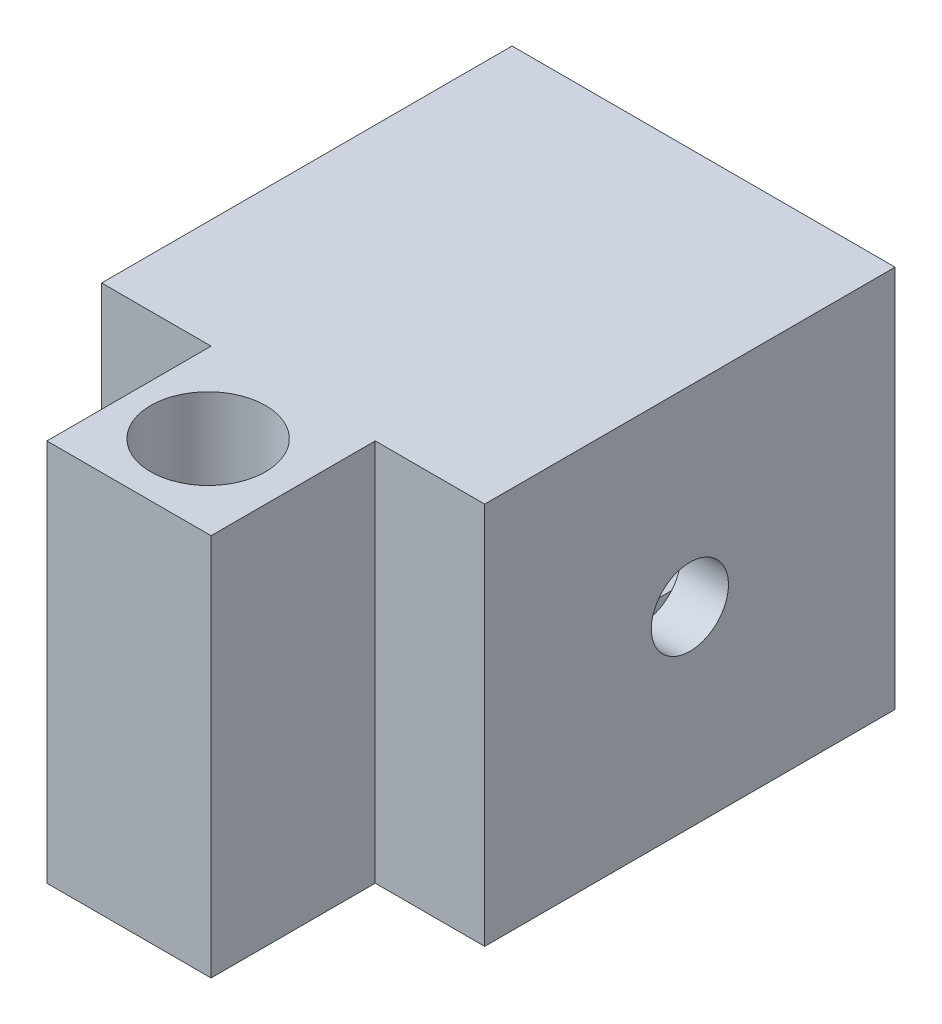
SolidWorks part; units mm, degrees
ref_plane "Спереди" through (0, 0, 0) normal (0, 0, 1) x (1, 0, 0)
ref_plane "Сверху" through (0, 0, 0) normal (0, 1, 0) x (1, 0, 0)
ref_plane "Справа" through (0, 0, 0) normal (1, 0, 0) x (0, 0, -1)
sketch "Эскиз2" plane through (0, 0, 0) normal (0, 0, 1) x (1, 0, 0)
  line L0 (10.5, 0) -> (-10.5, 0)
  line L1 (10.5, 10.5) -> (-10.5, 10.5)
  line L2 (10.5, 10.5) -> (10.5, -10.5)
  line L3 (10.5, -10.5) -> (-10.5, -10.5)
  line L4 (-10.5, 10.5) -> (-10.5, -10.5)
  line L5 (10.5, 10.5) -> (-10.5, -10.5) construction
  line L6 (10.5, -10.5) -> (-10.5, 10.5) construction
  line L7 (-14, 14) -> (14, 14)
  line L8 (-14, 14) -> (-14, -14)
  line L9 (-14, -14) -> (14, -14)
  line L10 (14, 14) -> (14, -14)
  line L11 (-14, 14) -> (14, -14) construction
  line L12 (-14, -14) -> (14, 14) construction
  line L13 (2.9067, -8.8) -> (2.9067, -10.5)
  line L14 (4.5056, -8.8) -> (2.9067, -8.8)
  line L15 (4.5056, -7.7999) -> (4.5056, -8.8)
  line L16 (-4.4952, -7.7999) -> (4.5056, -7.7999)
  line L17 (-4.4952, -8.8) -> (-4.4952, -7.7999)
  line L18 (-2.9933, -8.8) -> (-4.4952, -8.8)
  line L19 (-2.9933, -10.5) -> (-2.9933, -8.8)
  line L27 (-2.9933, 10.5) -> (-2.9933, 8.8)
  line L28 (-2.9933, 8.8) -> (-4.4952, 8.8)
  line L29 (-4.4952, 8.8) -> (-4.4952, 7.7999)
  line L30 (-4.4952, 7.7999) -> (4.5056, 7.7999)
  line L31 (4.5056, 7.7999) -> (4.5056, 8.8)
  line L32 (4.5056, 8.8) -> (2.9067, 8.8)
  line L33 (2.9067, 8.8) -> (2.9067, 10.5)
  point P0 (0, 0)
  point P6 (0, 0)
  dimension "D1" = 21
  dimension "D2" = 21
  dimension "D3" = 28
  dimension "D4" = 5.9
  dimension "D5" = 1.7
extrude "Бобышка-Вытянуть2" add sketch "Эскиз2" against normal blind 30 contours L19 L3 L13 L14 L15 L16 L17 L18 | L32 L33 L1 L27 L28 L29 L30 L31 region at (-0.0204, 9.0114, 0) region at (-0.0204, -9.0114, 0)
extrude "Бобышка-Вытянуть3" add sketch "Эскиз2<4>" against normal blind 5 contours L33 L32 L31 L30 L29 L28 L27 L1 L4 L0 L2 | L3 L19 L18 L17 L16 L15 L14 L13 L2 L0 L4 region at (0.0019, -4.8947, 0) region at (0.0019, 4.8947, 0)
sketch "Эскиз2<4>" plane through (0, 0, 0) normal (0, 0, 1) x (1, 0, 0) same geometry as "Эскиз2"
extrude "Бобышка-Вытянуть4" add sketch "Эскиз2<5>" against normal blind 30 contours L10 L7 L8 L9 L4 L1 L2 L3 region at (0, 13.604, 0)
sketch "Эскиз2<5>" plane through (0, 0, 0) normal (0, 0, 1) x (1, 0, 0) same geometry as "Эскиз2"
sketch "Эскиз5" plane through (-14, 0, 0) normal (-1, 0, 0) x (0, 0, 1)
  line L0 (0, 0) -> (-30, 0)
  line L1 (0, 14) -> (0, -14) construction
  line L2 (-30, 14) -> (-30, -14) construction
  circle A0 centre (-15, 0) radius 2.82
  dimension "D1" = 5.64
extrude "Вырез-Вытянуть1" cut sketch "Эскиз5" against normal through all contours L0 A0 | A0 region at (-14, -1.1968, -15)
sketch "Эскиз6" plane through (0, 0, 0) normal (0, 0, 1) x (1, 0, 0)
  line L1 (-6, -14) -> (6, -14)
  line L2 (-6, -14) -> (-6, 14)
  line L3 (-6, 14) -> (6, 14)
  line L4 (6, -14) -> (6, 14)
  line L5 (-6, -14) -> (6, 14) construction
  line L6 (-6, 14) -> (6, -14) construction
  point P0 (0, 0)
  dimension "D1" = 12
  dimension "D2" = 28
extrude "Бобышка-Вытянуть7" add sketch "Эскиз6" along normal blind 12 contours L4 L3 L2 L1
sketch "Эскиз9" plane through (0, -14, 0) normal (0, -1, 0) x (1, 0, 0)
  circle A0 centre (-0.252, 5.9646) radius 4.2
extrude "Вырез-Вытянуть3" cut sketch "Эскиз9" against normal through all
